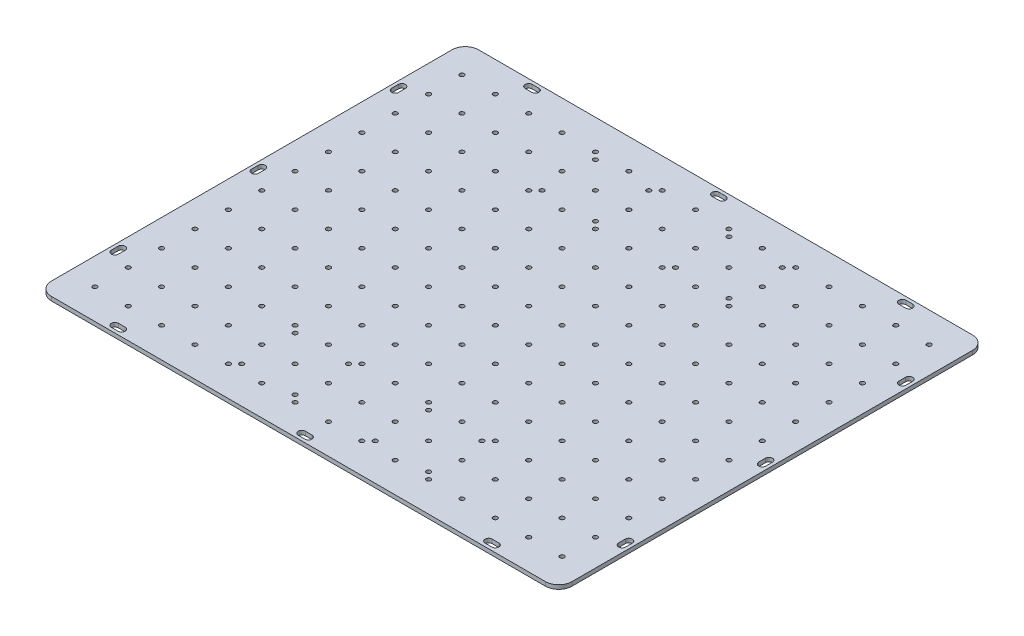
SolidWorks part; units mm, degrees
material "1060 Alloy"
ref_plane "Front Plane" through (0, 0, 0) normal (0, 0, 1) x (1, 0, 0)
ref_plane "Top Plane" through (0, 0, 0) normal (0, 1, 0) x (1, 0, 0)
ref_plane "Right Plane" through (0, 0, 0) normal (1, 0, 0) x (0, 0, -1)
sketch "Sketch1" plane through (0, 0, 0) normal (0, 1, 0) x (1, 0, 0)
  line L0 (52.5, 310) -> (47.5, 310) construction
  line L1 (0, 0) -> (380, 0) construction
  line L2 (0, 0) -> (0, 310) construction
  line L3 (0, 310) -> (380, 310) construction
  line L4 (380, 0) -> (380, 310) construction
  line L5 (190, 310) -> (190, 0) construction
  line L6 (0, 155) -> (380, 155) construction
  line L7 (385, -5) -> (-5, -5)
  line L8 (385, -5) -> (385, 315)
  line L9 (385, 315) -> (-5, 315)
  line L10 (-5, -5) -> (-5, 315)
  line L11 (190, 315) -> (190, -5) construction
  line L12 (385, 155) -> (-5, 155) construction
  line L13 (52.5, 307.35) -> (47.5, 307.35)
  line L14 (52.5, 312.65) -> (47.5, 312.65)
  line L15 (0, 257.5) -> (0, 262.5) construction
  line L16 (-2.65, 257.5) -> (-2.65, 262.5)
  line L17 (2.65, 257.5) -> (2.65, 262.5)
  line L18 (192.5, 310) -> (187.5, 310) construction
  line L19 (192.5, 307.35) -> (187.5, 307.35)
  line L20 (192.5, 312.65) -> (187.5, 312.65)
  line L21 (0, 152.5) -> (0, 157.5) construction
  line L22 (-2.65, 152.5) -> (-2.65, 157.5)
  line L23 (2.65, 152.5) -> (2.65, 157.5)
  line L24 (0, 47.5) -> (0, 52.5) construction
  line L25 (-2.65, 47.5) -> (-2.65, 52.5)
  line L26 (2.65, 47.5) -> (2.65, 52.5)
  line L27 (380, 257.5) -> (380, 262.5) construction
  line L28 (382.65, 257.5) -> (382.65, 262.5)
  line L29 (377.35, 257.5) -> (377.35, 262.5)
  line L30 (380, 152.5) -> (380, 157.5) construction
  line L31 (382.65, 152.5) -> (382.65, 157.5)
  line L32 (377.35, 152.5) -> (377.35, 157.5)
  line L33 (380, 47.5) -> (380, 52.5) construction
  line L34 (382.65, 47.5) -> (382.65, 52.5)
  line L35 (377.35, 47.5) -> (377.35, 52.5)
  line L36 (327.5, 310) -> (332.5, 310) construction
  line L37 (327.5, 307.35) -> (332.5, 307.35)
  line L38 (327.5, 312.65) -> (332.5, 312.65)
  line L39 (52.5, 0) -> (47.5, 0) construction
  line L40 (52.5, 2.65) -> (47.5, 2.65)
  line L41 (52.5, -2.65) -> (47.5, -2.65)
  line L42 (192.5, 0) -> (187.5, 0) construction
  line L43 (192.5, 2.65) -> (187.5, 2.65)
  line L44 (192.5, -2.65) -> (187.5, -2.65)
  line L45 (327.5, 0) -> (332.5, 0) construction
  line L46 (327.5, 2.65) -> (332.5, 2.65)
  line L47 (327.5, -2.65) -> (332.5, -2.65)
  circle A0 centre (190, 310) radius 1.65 construction
  circle A1 centre (50, 310) radius 1.65 construction
  circle A2 centre (0, 50) radius 1.65 construction
  circle A3 centre (0, 260) radius 1.65 construction
  circle A4 centre (0, 155) radius 1.65 construction
  circle A5 centre (380, 50) radius 1.65 construction
  circle A6 centre (380, 155) radius 1.65 construction
  circle A7 centre (380, 260) radius 1.65 construction
  circle A8 centre (330, 310) radius 1.65 construction
  arc A9 (52.5, 307.35) -> (52.5, 312.65) centre (52.5, 310) ccw
  arc A10 (47.5, 312.65) -> (47.5, 307.35) centre (47.5, 310) ccw
  arc A11 (-2.65, 257.5) -> (2.65, 257.5) centre (0, 257.5) ccw
  arc A12 (2.65, 262.5) -> (-2.65, 262.5) centre (0, 262.5) ccw
  arc A13 (192.5, 307.35) -> (192.5, 312.65) centre (192.5, 310) ccw
  arc A14 (187.5, 312.65) -> (187.5, 307.35) centre (187.5, 310) ccw
  arc A15 (-2.65, 152.5) -> (2.65, 152.5) centre (0, 152.5) ccw
  arc A16 (2.65, 157.5) -> (-2.65, 157.5) centre (0, 157.5) ccw
  arc A17 (-2.65, 47.5) -> (2.65, 47.5) centre (0, 47.5) ccw
  arc A18 (2.65, 52.5) -> (-2.65, 52.5) centre (0, 52.5) ccw
  arc A19 (382.65, 257.5) -> (377.35, 257.5) centre (380, 257.5) cw
  arc A20 (377.35, 262.5) -> (382.65, 262.5) centre (380, 262.5) cw
  arc A21 (382.65, 152.5) -> (377.35, 152.5) centre (380, 152.5) cw
  arc A22 (377.35, 157.5) -> (382.65, 157.5) centre (380, 157.5) cw
  arc A23 (382.65, 47.5) -> (377.35, 47.5) centre (380, 47.5) cw
  arc A24 (377.35, 52.5) -> (382.65, 52.5) centre (380, 52.5) cw
  arc A25 (327.5, 307.35) -> (327.5, 312.65) centre (327.5, 310) cw
  arc A26 (332.5, 312.65) -> (332.5, 307.35) centre (332.5, 310) cw
  arc A27 (52.5, 2.65) -> (52.5, -2.65) centre (52.5, 0) cw
  arc A28 (47.5, -2.65) -> (47.5, 2.65) centre (47.5, 0) cw
  arc A29 (192.5, 2.65) -> (192.5, -2.65) centre (192.5, 0) cw
  arc A30 (187.5, -2.65) -> (187.5, 2.65) centre (187.5, 0) cw
  arc A31 (327.5, 2.65) -> (327.5, -2.65) centre (327.5, 0) ccw
  arc A32 (332.5, -2.65) -> (332.5, 2.65) centre (332.5, 0) ccw
  point P21 (190, 155)
  point P26 (50, 310)
  point P33 (0, 260)
  point P40 (190, 310)
  point P47 (0, 155)
  point P54 (0, 50)
  point P61 (380, 260)
  point P68 (190, 155)
  point P73 (380, 155)
  point P80 (380, 50)
  point P87 (330, 310)
  point P94 (50, 0)
  point P101 (190, 0)
  point P108 (330, 0)
  point P113 (0, 0)
  dimension "D1" = 3.3
  dimension "D2" = 140
  dimension "D3" = 50
  dimension "D4" = 50
  dimension "D5" = 105
  dimension "D6" = 105
  dimension "D7" = 5
  dimension "D8" = 5
  dimension "D9" = 5.3
  dimension "D10" = 5
  dimension "D11" = 5.3
  dimension "D12" = 5
  dimension "D13" = 5.3
  dimension "D14" = 5
  dimension "D15" = 5.3
  dimension "D16" = 5
  dimension "D17" = 5.3
  dimension "D18" = 5
extrude "Boss-Extrude1" add sketch "Sketch1" along normal blind 3
sketch "Sketch3" plane through (0, 3, 0) normal (0, 1, 0) x (1, 0, 0)
  line L0 (-5, 315) -> (-5, -5) construction
  line L1 (385, 315) -> (-5, 315) construction
  circle A0 centre (15, 292.5) radius 1.65
  circle A1 centre (40, 292.5) radius 1.65
  circle A2 centre (65, 292.5) radius 1.65
  circle A3 centre (90, 292.5) radius 1.65
  circle A4 centre (115, 292.5) radius 1.65
  circle A5 centre (140, 292.5) radius 1.65
  circle A6 centre (165, 292.5) radius 1.65
  circle A7 centre (190, 292.5) radius 1.65
  circle A8 centre (215, 292.5) radius 1.65
  circle A9 centre (240, 292.5) radius 1.65
  circle A10 centre (265, 292.5) radius 1.65
  circle A11 centre (290, 292.5) radius 1.65
  circle A12 centre (315, 292.5) radius 1.65
  circle A13 centre (340, 292.5) radius 1.65
  circle A14 centre (365, 292.5) radius 1.65
  circle A15 centre (40, 267.5) radius 1.65
  circle A16 centre (65, 267.5) radius 1.65
  circle A17 centre (90, 267.5) radius 1.65
  circle A18 centre (115, 267.5) radius 1.65
  circle A19 centre (140, 267.5) radius 1.65
  circle A20 centre (165, 267.5) radius 1.65
  circle A21 centre (190, 267.5) radius 1.65
  circle A22 centre (215, 267.5) radius 1.65
  circle A23 centre (240, 267.5) radius 1.65
  circle A24 centre (265, 267.5) radius 1.65
  circle A25 centre (290, 267.5) radius 1.65
  circle A26 centre (315, 267.5) radius 1.65
  circle A27 centre (340, 267.5) radius 1.65
  circle A28 centre (365, 267.5) radius 1.65
  circle A29 centre (40, 242.5) radius 1.65
  circle A30 centre (65, 242.5) radius 1.65
  circle A31 centre (90, 242.5) radius 1.65
  circle A32 centre (115, 242.5) radius 1.65
  circle A33 centre (140, 242.5) radius 1.65
  circle A34 centre (165, 242.5) radius 1.65
  circle A35 centre (190, 242.5) radius 1.65
  circle A36 centre (215, 242.5) radius 1.65
  circle A37 centre (240, 242.5) radius 1.65
  circle A38 centre (265, 242.5) radius 1.65
  circle A39 centre (290, 242.5) radius 1.65
  circle A40 centre (315, 242.5) radius 1.65
  circle A41 centre (340, 242.5) radius 1.65
  circle A42 centre (365, 242.5) radius 1.65
  circle A43 centre (40, 217.5) radius 1.65
  circle A44 centre (65, 217.5) radius 1.65
  circle A45 centre (90, 217.5) radius 1.65
  circle A46 centre (115, 217.5) radius 1.65
  circle A47 centre (140, 217.5) radius 1.65
  circle A48 centre (165, 217.5) radius 1.65
  circle A49 centre (190, 217.5) radius 1.65
  circle A50 centre (215, 217.5) radius 1.65
  circle A51 centre (240, 217.5) radius 1.65
  circle A52 centre (265, 217.5) radius 1.65
  circle A53 centre (290, 217.5) radius 1.65
  circle A54 centre (315, 217.5) radius 1.65
  circle A55 centre (340, 217.5) radius 1.65
  circle A56 centre (365, 217.5) radius 1.65
  circle A57 centre (40, 192.5) radius 1.65
  circle A58 centre (65, 192.5) radius 1.65
  circle A59 centre (90, 192.5) radius 1.65
  circle A60 centre (115, 192.5) radius 1.65
  circle A61 centre (140, 192.5) radius 1.65
  circle A62 centre (165, 192.5) radius 1.65
  circle A63 centre (190, 192.5) radius 1.65
  circle A64 centre (215, 192.5) radius 1.65
  circle A65 centre (240, 192.5) radius 1.65
  circle A66 centre (265, 192.5) radius 1.65
  circle A67 centre (290, 192.5) radius 1.65
  circle A68 centre (315, 192.5) radius 1.65
  circle A69 centre (340, 192.5) radius 1.65
  circle A70 centre (365, 192.5) radius 1.65
  circle A71 centre (40, 167.5) radius 1.65
  circle A72 centre (65, 167.5) radius 1.65
  circle A73 centre (90, 167.5) radius 1.65
  circle A74 centre (115, 167.5) radius 1.65
  circle A75 centre (140, 167.5) radius 1.65
  circle A76 centre (165, 167.5) radius 1.65
  circle A77 centre (190, 167.5) radius 1.65
  circle A78 centre (215, 167.5) radius 1.65
  circle A79 centre (240, 167.5) radius 1.65
  circle A80 centre (265, 167.5) radius 1.65
  circle A81 centre (290, 167.5) radius 1.65
  circle A82 centre (315, 167.5) radius 1.65
  circle A83 centre (340, 167.5) radius 1.65
  circle A84 centre (365, 167.5) radius 1.65
  circle A85 centre (40, 142.5) radius 1.65
  circle A86 centre (65, 142.5) radius 1.65
  circle A87 centre (90, 142.5) radius 1.65
  circle A88 centre (115, 142.5) radius 1.65
  circle A89 centre (140, 142.5) radius 1.65
  circle A90 centre (165, 142.5) radius 1.65
  circle A91 centre (190, 142.5) radius 1.65
  circle A92 centre (215, 142.5) radius 1.65
  circle A93 centre (240, 142.5) radius 1.65
  circle A94 centre (265, 142.5) radius 1.65
  circle A95 centre (290, 142.5) radius 1.65
  circle A96 centre (315, 142.5) radius 1.65
  circle A97 centre (340, 142.5) radius 1.65
  circle A98 centre (365, 142.5) radius 1.65
  circle A99 centre (40, 117.5) radius 1.65
  circle A100 centre (65, 117.5) radius 1.65
  circle A101 centre (90, 117.5) radius 1.65
  circle A102 centre (115, 117.5) radius 1.65
  circle A103 centre (140, 117.5) radius 1.65
  circle A104 centre (165, 117.5) radius 1.65
  circle A105 centre (190, 117.5) radius 1.65
  circle A106 centre (215, 117.5) radius 1.65
  circle A107 centre (240, 117.5) radius 1.65
  circle A108 centre (265, 117.5) radius 1.65
  circle A109 centre (290, 117.5) radius 1.65
  circle A110 centre (315, 117.5) radius 1.65
  circle A111 centre (340, 117.5) radius 1.65
  circle A112 centre (365, 117.5) radius 1.65
  circle A113 centre (40, 92.5) radius 1.65
  circle A114 centre (65, 92.5) radius 1.65
  circle A115 centre (90, 92.5) radius 1.65
  circle A116 centre (115, 92.5) radius 1.65
  circle A117 centre (140, 92.5) radius 1.65
  circle A118 centre (165, 92.5) radius 1.65
  circle A119 centre (190, 92.5) radius 1.65
  circle A120 centre (215, 92.5) radius 1.65
  circle A121 centre (240, 92.5) radius 1.65
  circle A122 centre (265, 92.5) radius 1.65
  circle A123 centre (290, 92.5) radius 1.65
  circle A124 centre (315, 92.5) radius 1.65
  circle A125 centre (340, 92.5) radius 1.65
  circle A126 centre (365, 92.5) radius 1.65
  circle A127 centre (40, 67.5) radius 1.65
  circle A128 centre (65, 67.5) radius 1.65
  circle A129 centre (90, 67.5) radius 1.65
  circle A130 centre (115, 67.5) radius 1.65
  circle A131 centre (140, 67.5) radius 1.65
  circle A132 centre (165, 67.5) radius 1.65
  circle A133 centre (190, 67.5) radius 1.65
  circle A134 centre (215, 67.5) radius 1.65
  circle A135 centre (240, 67.5) radius 1.65
  circle A136 centre (265, 67.5) radius 1.65
  circle A137 centre (290, 67.5) radius 1.65
  circle A138 centre (315, 67.5) radius 1.65
  circle A139 centre (340, 67.5) radius 1.65
  circle A140 centre (365, 67.5) radius 1.65
  circle A141 centre (40, 42.5) radius 1.65
  circle A142 centre (65, 42.5) radius 1.65
  circle A143 centre (90, 42.5) radius 1.65
  circle A144 centre (115, 42.5) radius 1.65
  circle A145 centre (140, 42.5) radius 1.65
  circle A146 centre (165, 42.5) radius 1.65
  circle A147 centre (190, 42.5) radius 1.65
  circle A148 centre (215, 42.5) radius 1.65
  circle A149 centre (240, 42.5) radius 1.65
  circle A150 centre (265, 42.5) radius 1.65
  circle A151 centre (290, 42.5) radius 1.65
  circle A152 centre (315, 42.5) radius 1.65
  circle A153 centre (340, 42.5) radius 1.65
  circle A154 centre (365, 42.5) radius 1.65
  circle A155 centre (40, 17.5) radius 1.65
  circle A156 centre (65, 17.5) radius 1.65
  circle A157 centre (90, 17.5) radius 1.65
  circle A158 centre (115, 17.5) radius 1.65
  circle A159 centre (140, 17.5) radius 1.65
  circle A160 centre (165, 17.5) radius 1.65
  circle A161 centre (190, 17.5) radius 1.65
  circle A162 centre (215, 17.5) radius 1.65
  circle A163 centre (240, 17.5) radius 1.65
  circle A164 centre (265, 17.5) radius 1.65
  circle A165 centre (290, 17.5) radius 1.65
  circle A166 centre (315, 17.5) radius 1.65
  circle A167 centre (340, 17.5) radius 1.65
  circle A168 centre (365, 17.5) radius 1.65
  circle A169 centre (15, 267.5) radius 1.65
  circle A170 centre (15, 242.5) radius 1.65
  circle A171 centre (15, 217.5) radius 1.65
  circle A172 centre (15, 192.5) radius 1.65
  circle A173 centre (15, 167.5) radius 1.65
  circle A174 centre (15, 142.5) radius 1.65
  circle A175 centre (15, 117.5) radius 1.65
  circle A176 centre (15, 92.5) radius 1.65
  circle A177 centre (15, 67.5) radius 1.65
  circle A178 centre (15, 42.5) radius 1.65
  circle A179 centre (15, 17.5) radius 1.65
  point P2 (0, 0)
  point P8 (0, 0)
  dimension "D1" = 3.3
  dimension "D2" = 20
  dimension "D3" = 22.5
  dimension "D6" = 25
  dimension "D7" = 25
  dimension "D4" = 15
  dimension "D5" = 12
extrude "Cut-Extrude2" cut sketch "Sketch3" against normal through all
sketch "Sketch4" plane through (0, 3, 0) normal (0, 1, 0) x (1, 0, 0)
  line L0 (190, -5) -> (190, 315) construction
  line L1 (-5, -5) -> (385, -5) construction
  line L2 (385, 315) -> (-5, 315) construction
  line L3 (-5, 155) -> (385, 155) construction
  line L4 (120, 62.5) -> (160, 62.5) construction
  line L5 (120, 62.5) -> (120, 22.5) construction
  line L6 (120, 22.5) -> (160, 22.5) construction
  line L7 (160, 62.5) -> (160, 22.5) construction
  line L8 (140, 22.5) -> (140, 62.5) construction
  line L9 (120, 42.5) -> (160, 42.5) construction
  line L10 (-5, 315) -> (-5, -5) construction
  line L11 (385, -5) -> (385, 315) construction
  circle A0 centre (120, 62.5) radius 1.65
  circle A1 centre (160, 62.5) radius 1.65
  circle A2 centre (120, 22.5) radius 1.65
  circle A3 centre (160, 22.5) radius 1.65
  circle A4 centre (260, 62.5) radius 1.65
  circle A5 centre (260, 22.5) radius 1.65
  circle A6 centre (220, 22.5) radius 1.65
  circle A7 centre (220, 62.5) radius 1.65
  circle A8 centre (260, 247.5) radius 1.65
  circle A9 centre (260, 287.5) radius 1.65
  circle A10 centre (220, 287.5) radius 1.65
  circle A11 centre (220, 247.5) radius 1.65
  circle A12 centre (120, 287.5) radius 1.65
  circle A13 centre (160, 287.5) radius 1.65
  circle A14 centre (160, 247.5) radius 1.65
  circle A15 centre (120, 247.5) radius 1.65
  point P6 (140, 42.5)
  dimension "D3" = 3.3
  dimension "D1" = 40
  dimension "D2" = 40
extrude "Cut-Extrude3" cut sketch "Sketch4" against normal through all
fillet "Fillet1" radius 10 4 edges at (385, 1.5, -315) (385, 1.5, 5) (-5, 1.5, 5) (-5, 1.5, -315)
